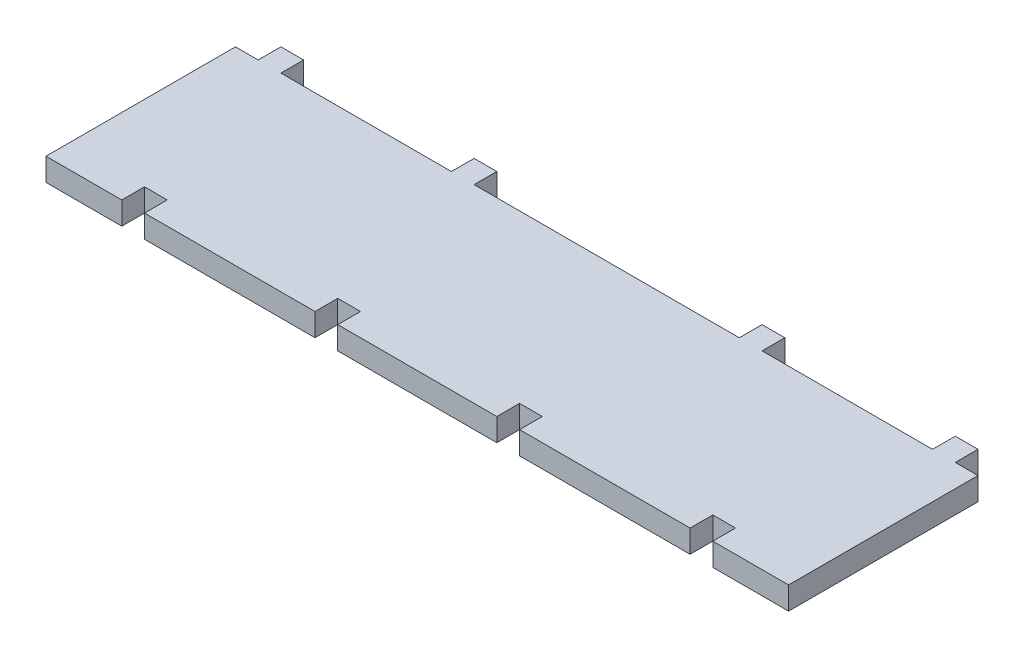
SolidWorks part; units mm, degrees
material "Pine"
ref_plane "정면" through (0, 0, 0) normal (0, 0, 1) x (1, 0, 0)
ref_plane "윗면" through (0, 0, 0) normal (0, 1, 0) x (1, 0, 0)
ref_plane "우측면" through (0, 0, 0) normal (1, 0, 0) x (0, 0, -1)
sketch "Sketch1" plane through (0, 0, 0) normal (0, 0, 1) x (1, 0, 0)
  line L0 (0, -55.5594) -> (0, 89.4924) construction
  line L1 (98, 0) -> (-98, 0)
  line L2 (-98, 0) -> (-98, 6)
  line L3 (-98, 6) -> (98, 6)
  line L4 (98, 0) -> (98, 6)
  point P8 (0, 6)
  point P9 (0, 0)
  dimension "D1" = 98
  dimension "D2" = 6
extrude "Boss-Extrude1" add sketch "Sketch1" along normal blind 50
sketch "Sketch2" plane through (0, 0, 0) normal (0, 0, -1) x (-1, 0, 0)
  line L0 (0, -28.0858) -> (0, 36.535) construction
  line L1 (98, 0) -> (-98, 0) construction
  line L2 (-92, 0) -> (-92, 6)
  line L3 (-98, 6) -> (98, 6) construction
  line L4 (-92, 6) -> (-86, 6)
  line L5 (-86, 6) -> (-86, 0)
  line L6 (-86, 0) -> (-92, 0)
  line L7 (-98, 0) -> (-98, 6) construction
  line L8 (-41, 0) -> (-41, 6)
  line L9 (-41, 6) -> (-35, 6)
  line L10 (-35, 6) -> (-35, 0)
  line L11 (-35, 0) -> (-41, 0)
  line L12 (35, 0) -> (41, 0)
  line L13 (35, 6) -> (35, 0)
  line L14 (41, 6) -> (35, 6)
  line L15 (41, 0) -> (41, 6)
  line L16 (86, 0) -> (92, 0)
  line L17 (86, 6) -> (86, 0)
  line L18 (92, 6) -> (86, 6)
  line L19 (92, 0) -> (92, 6)
  point P17 (-38, 6)
  dimension "D1" = 6
  dimension "D2" = 6
  dimension "D3" = 6
  dimension "D4" = 6
  dimension "D5" = 6
  dimension "D6" = 45
  dimension "D7" = 6
extrude "Boss-Extrude2" add sketch "Sketch2" along normal blind 6
sketch "Sketch3" plane through (0, 6, 0) normal (0, 1, 0) x (1, 0, 0)
  line L0 (0, 40.6529) -> (0, -78.0081) construction
  line L1 (78, -50) -> (78, -44)
  line L2 (78, -44) -> (72, -44)
  line L3 (72, -44) -> (72, -50)
  line L4 (72, -50) -> (78, -50)
  line L5 (98, -50) -> (98, 0) construction
  line L6 (98, -50) -> (-98, -50) construction
  line L7 (27, -50) -> (27, -44)
  line L8 (27, -44) -> (21, -44)
  line L9 (21, -44) -> (21, -50)
  line L10 (21, -50) -> (27, -50)
  line L11 (-21, -50) -> (-27, -50)
  line L12 (-21, -44) -> (-21, -50)
  line L13 (-27, -44) -> (-21, -44)
  line L14 (-27, -50) -> (-27, -44)
  line L15 (-72, -50) -> (-78, -50)
  line L16 (-72, -44) -> (-72, -50)
  line L17 (-78, -44) -> (-72, -44)
  line L18 (-78, -50) -> (-78, -44)
  dimension "D1" = 6
  dimension "D2" = 6
  dimension "D3" = 20
  dimension "D4" = 45
  dimension "D5" = 6
  dimension "D6" = 6
extrude "Cut-Extrude1" cut sketch "Sketch3" against normal blind 6
sketch "Sketch4" plane through (0, 6, 0) normal (0, 1, 0) x (1, 0, 0)
  line L0 (0, 50.3189) -> (0, -101.6218) construction
